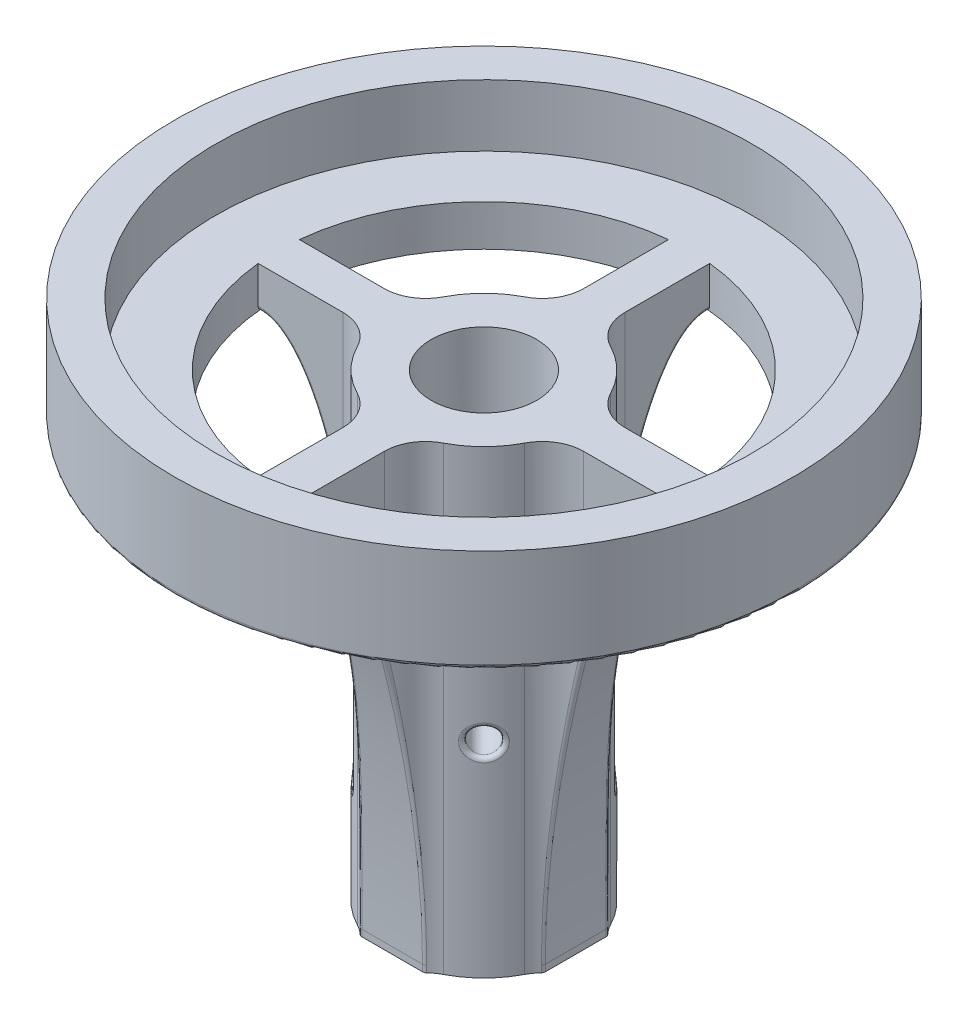
SolidWorks part; units mm, degrees
ref_plane "Front Plane" through (0, 0, 0) normal (0, 0, 1) x (1, 0, 0)
ref_plane "Top Plane" through (0, 0, 0) normal (0, 1, 0) x (1, 0, 0)
ref_plane "Right Plane" through (0, 0, 0) normal (1, 0, 0) x (0, 0, -1)
sketch "Sketch1" plane through (0, 0, 0) normal (0, 1, 0) x (1, 0, 0)
  circle A0 centre (0, 0) radius 75
  circle A1 centre (0, 0) radius 65
  dimension "D1" = 150
  dimension "D2" = 10
extrude "Boss-Extrude1" add sketch "Sketch1" along normal blind 15
extrude "Boss-Extrude2" add sketch "Sketch1<2>" against normal blind 10 contours A1 | A0 A1 region at (-72.8787, 0, 0) region at (0, 0, 0)
sketch "Sketch1<2>" plane through (0, 0, 0) normal (0, 1, 0) x (1, 0, 0) same geometry as "Sketch1"
sketch "Sketch2" plane through (0, -10, 0) normal (0, 1, 0) x (1, 0, 0)
  line L0 (-22.245, 5) -> (-22.245, -5)
  line L1 (-22.245, -5) -> (-50.555, -5)
  line L2 (0, -50) -> (0, -22.8) construction
  line L3 (-22.245, 5) -> (-50.555, 5)
  line L4 (-50.555, 5) -> (-50.555, -5)
  line L5 (-5, -22.245) -> (5, -22.245)
  line L6 (-5, -22.245) -> (-5, -50.555)
  line L7 (-5, -50.555) -> (5, -50.555)
  line L8 (5, -22.245) -> (5, -50.555)
  line L9 (-5, -22.245) -> (5, -50.555) construction
  line L10 (-5, -50.555) -> (5, -22.245) construction
  line L11 (5, 22.245) -> (-5, 22.245)
  line L12 (-5, 22.245) -> (-5, 50.555)
  line L13 (5, 22.245) -> (5, 50.555)
  line L14 (5, 50.555) -> (-5, 50.555)
  line L15 (22.245, -5) -> (22.245, 5)
  line L16 (22.245, 5) -> (50.555, 5)
  line L17 (22.245, -5) -> (50.555, -5)
  line L18 (50.555, -5) -> (50.555, 5)
  circle A0 centre (0, 0) radius 50
  circle A1 centre (0, 0) radius 65 construction
  circle A2 centre (0, 0) radius 12.8
  circle A3 centre (0, 0) radius 22.8
  point P7 (0, 0)
  point P15 (0, -36.4)
  point P29 (0, 0)
  dimension "D1" = 15
  dimension "D2" = 25.6
  dimension "D3" = 10
  dimension "D4" = 10
  dimension "D5" = 4
extrude "Cut-Extrude1" cut sketch "Sketch2" along normal through all contours L16 A3 L13 A0 | L8 A3 L17 A0 | L1 A3 L6 A0 | L12 A3 L3 A0 | A2 region at (-25.2873, -10, -25.2873) region at (-25.2873, -10, 25.2873) region at (25.2873, -10, -25.2873) region at (25.2873, -10, 25.2873) region at (0, -10, 0)
extrude "Boss-Extrude3" add sketch "Sketch2<3>" against normal blind 101.6 contours A3 L11 L15 L5 L0 A2 region at (-15.6771, -10, -15.6771)
sketch "Sketch2<3>" plane through (0, -10, 0) normal (0, 1, 0) x (1, 0, 0) same geometry as "Sketch2"
fillet "Fillet1" radius 100 4 edges at (-22.245, -10, 0) (0, -10, -22.245) (22.245, -10, 0) (0, -10, 22.245) second distance 27 first distance on face at (-22.245, -60.8, 0) first distance on face at (0, -60.8, -22.245) first distance on face at (22.245, -60.8, 0) first distance on face at (0, -60.8, 22.245)
fillet "Fillet2" radius 10 8 edges
fillet "Fillet3" radius 1 34 edges at (-22.7905, -90, 7.2985) (-25.4434, -62.7892, -5.72) (-7.2985, -90, -22.7905) (5.72, -62.7892, -25.4434) (-5.72, -62.7892, 25.4434) (7.2985, -90, 22.7905) (25.4434, -62.7892, 5.72) (22.7905, -90, -7.2985) (0, -111.6, -12.8) (0, -10, 75)
ref_plane "Plane1" through (0, 0, 0) normal (0.7071, 0, -0.7071) x (-0.7071, 0, -0.7071)
sketch "Sketch3" plane through (0, 0, 0) normal (0.7071, 0, -0.7071) x (-0.7071, 0, -0.7071)
  line L0 (0, -40) -> (0, -84.45) construction
  line L1 (3.175, -40) -> (3.175, -84.45)
  line L2 (-3.175, -40) -> (-3.175, -84.45)
  line L4 (6.9645, 0) -> (-6.9645, 0) construction
  arc A0 (3.175, -40) -> (-3.175, -40) centre (0, -40) ccw
  arc A1 (-3.175, -84.45) -> (3.175, -84.45) centre (0, -84.45) ccw
  point P3 (0, -62.225)
  dimension "D1" = 6.35
  dimension "D2" = 44.45
  dimension "D3" = 40
extrude "Cut-Extrude2" cut sketch "Sketch3" against normal through all both and the other way through all
sketch "Sketch4" plane through (2.2451, 0, 2.2451) normal (-0.7071, 0, -0.7071) x (-0.7071, 0, 0.7071)
  line L0 (12.4, -62.225) -> (-12.4, -62.225) construction
  line L1 (12.4, -40) -> (12.4, -84.45) construction
  line L2 (-12.4, -84.45) -> (-12.4, -40) construction
  circle A0 centre (0, -62.225) radius 3.175
  point P2 (0, 0)
  point P9 (0, -62.225)
  dimension "D1" = 6.35
extrude "Cut-Extrude3" cut sketch "Sketch4" along normal through all and the other way through all
fillet "Fillet4" radius 1 10 edges at (16.3696, -87.6053, -15.8706) (13.7199, -62.225, -18.21) (15.8706, -36.8447, -16.3696) (-15.8706, -36.8447, 16.3696) (-18.21, -62.225, 13.7199) (-16.3696, -87.6053, 15.8706) (18.21, -62.225, -13.7199) (-18.163, -61.5292, -13.782) (13.782, -62.9208, 18.163) (-13.7199, -62.225, 18.21)
